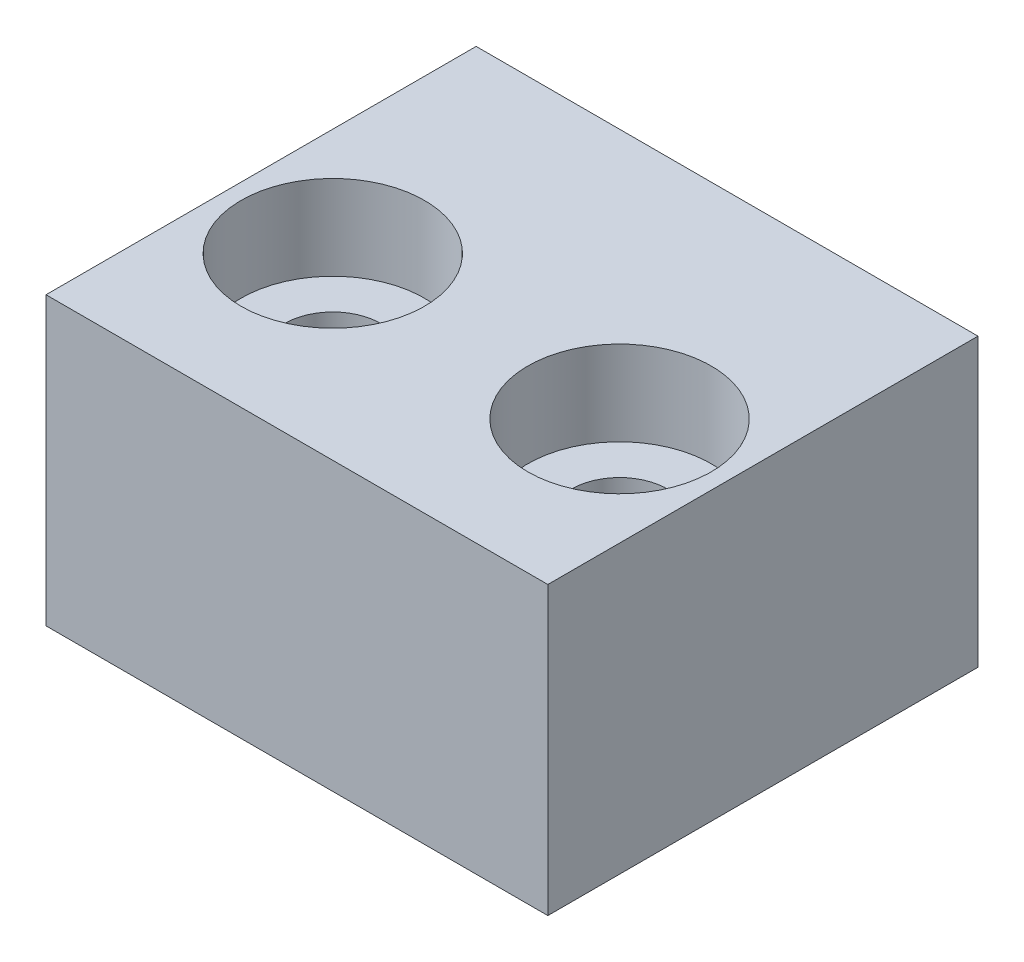
SolidWorks part; units mm, degrees
ref_plane "Front Plane" through (0, 0, 0) normal (0, 0, 1) x (1, 0, 0)
ref_plane "Top Plane" through (0, 0, 0) normal (0, 1, 0) x (1, 0, 0)
ref_plane "Right Plane" through (0, 0, 0) normal (1, 0, 0) x (0, 0, -1)
sketch "Sketch1" plane through (0, 0, 0) normal (0, 1, 0) x (1, 0, 0)
  line L0 (3.81, 6.35) -> (13.97, 6.35) construction
  line L1 (0, 0) -> (17.78, 0)
  line L2 (0, 0) -> (0, 15.24)
  line L3 (0, 15.24) -> (17.78, 15.24)
  line L4 (17.78, 0) -> (17.78, 15.24)
  line L5 (8.89, 15.24) -> (8.89, 0) construction
  dimension "D2" = 6.35
  dimension "D1" = 15.24
  dimension "D3" = 17.78
  dimension "D4" = 10.16
extrude "Boss-Extrude1" add sketch "Sketch1" along normal blind 10.16
sketch "Sketch6" plane through (0, 10.16, 0) normal (0, 1, 0) x (1, 0, 0)
  point P0 (3.81, 6.35)
  point P3 (13.97, 6.35)
hole_wizard "CBORE for M3 SHCS1" positions "Sketch6" profile "Sketch5" counterbore size "M3" standard "ANSI Metric" end condition through all
sketch "Sketch5" plane through (3.81, 10.16, -6.35) normal (1, 0, 0) x (0, 0, 1)
  line L0 (0, 0) -> (0, 10.16)
  line L1 (0, 10.16) -> (1.7, 10.16)
  line L3 (1.7, 10.16) -> (1.7, 3)
  line L4 (1.7, 3) -> (3.25, 3)
  line L5 (3.25, 3) -> (3.25, 0)
  line L7 (3.25, 0) -> (0, 0)
  line L11 (0, -6.35) -> (0, 107.95) construction
  dimension "Thru Hole Dia." = 3.4
  dimension "Thru Hole Depth" = 10.16
  dimension "C'Bore Dia." = 6.5
  dimension "C'Bore Depth" = 3
